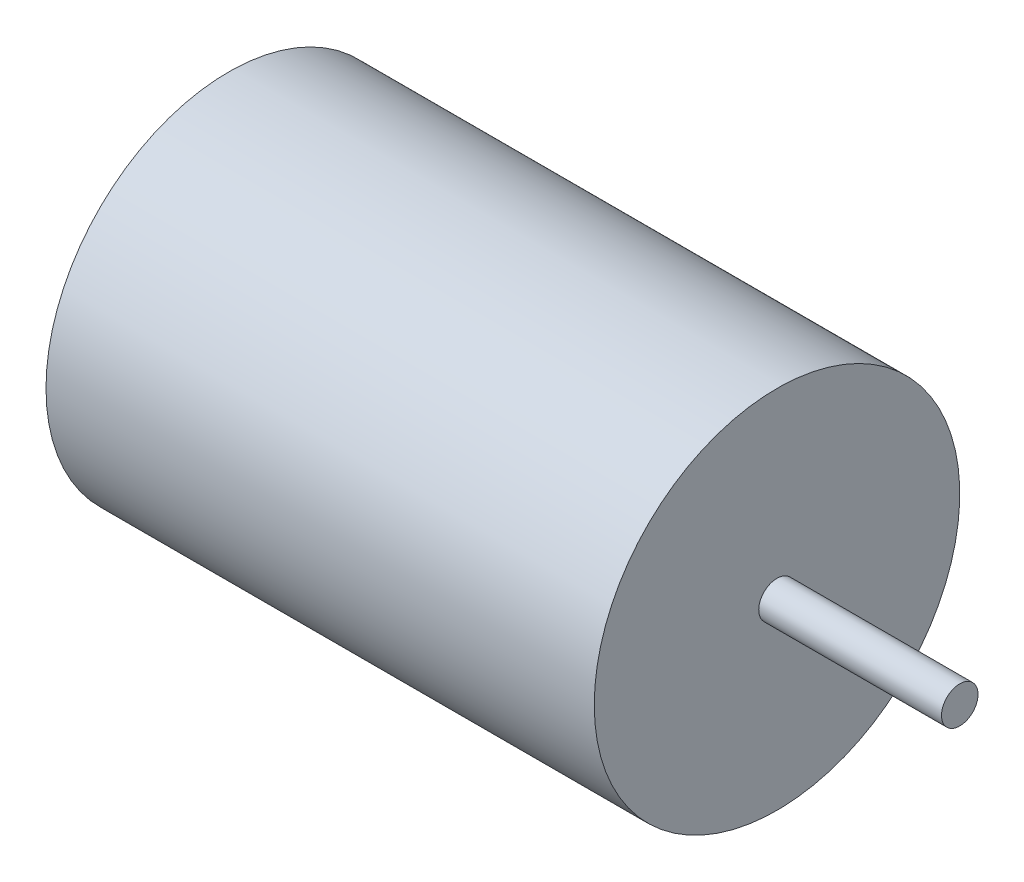
SolidWorks part; units mm, degrees
ref_plane "Plan de face" through (0, 0, 0) normal (0, 0, 1) x (1, 0, 0)
ref_plane "Plan de dessus" through (0, 0, 0) normal (0, 1, 0) x (1, 0, 0)
ref_plane "Plan de droite" through (0, 0, 0) normal (1, 0, 0) x (0, 0, -1)
sketch "Esquisse1" plane through (0, 0, 0) normal (0, 0, 1) x (1, 0, 0)
  line L0 (-38.2151, 0) -> (28.0969, 0) construction
  line L1 (10, 0) -> (10, 1)
  line L2 (10, 1) -> (0, 1)
  line L3 (0, 1) -> (0, 10)
  line L4 (0, 10) -> (-30, 10)
  line L5 (-30, 10) -> (-30, 0)
  line L6 (-30, 0) -> (10, 0)
  dimension "D1" = 2
  dimension "D2" = 20
  dimension "D3" = 10
  dimension "D4" = 30
revolve "Révolution1" add sketch "Esquisse1" angle 360 about L0
